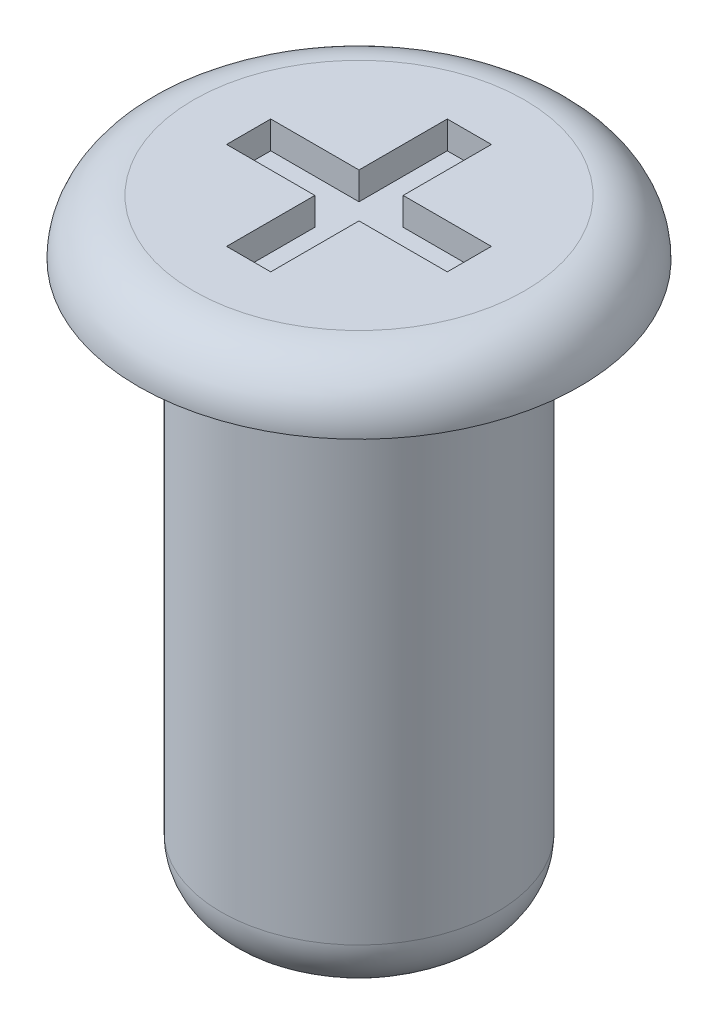
SolidWorks part; units mm, degrees
material "1060 Alloy"
ref_plane "Front Plane" through (0, 0, 0) normal (0, 0, 1) x (1, 0, 0)
ref_plane "Top Plane" through (0, 0, 0) normal (0, 1, 0) x (1, 0, 0)
ref_plane "Right Plane" through (0, 0, 0) normal (1, 0, 0) x (0, 0, -1)
sketch "Sketch1" plane through (0, 0, 0) normal (0, 1, 0) x (1, 0, 0)
  circle A0 centre (0, 0) radius 6.35
  dimension "D1" = 12.7
extrude "Boss-Extrude1" add sketch "Sketch1" along normal blind 25.4
cosmetic thread "Cosmetic Thread3" parameters "D1"=5, "D2"=10.3734
sketch "Sketch2" plane through (0, 25.4, 0) normal (0, 1, 0) x (1, 0, 0)
  circle A0 centre (0, 0) radius 10.16
  dimension "D1" = 20.32
extrude "Boss-Extrude2" add sketch "Sketch2" along normal blind 2.54
fillet "Fillet1" radius 2.54 1 edges at (0, 27.94, 10.16)
sketch "Sketch3" plane through (0, 27.94, 0) normal (0, 1, 0) x (1, 0, 0)
  line L1 (-1.016, -5.08) -> (1.016, -5.08)
  line L2 (-1.016, -5.08) -> (-1.016, 5.08)
  line L3 (-1.016, 5.08) -> (1.016, 5.08)
  line L4 (1.016, -5.08) -> (1.016, 5.08)
  line L5 (-1.016, -5.08) -> (1.016, 5.08) construction
  line L6 (-1.016, 5.08) -> (1.016, -5.08) construction
  line L7 (-5.08, 1.016) -> (5.08, 1.016)
  line L8 (-5.08, 1.016) -> (-5.08, -1.016)
  line L9 (-5.08, -1.016) -> (5.08, -1.016)
  line L10 (5.08, 1.016) -> (5.08, -1.016)
  line L11 (-5.08, 1.016) -> (5.08, -1.016) construction
  line L12 (-5.08, -1.016) -> (5.08, 1.016) construction
  point P0 (0, 0)
  point P6 (0, 0)
  dimension "D1" = 2.032
  dimension "D2" = 2.032
  dimension "D3" = 10.16
  dimension "D4" = 10.16
extrude "Cut-Extrude1" cut sketch "Sketch3" against normal blind 1.27 contours L8 L9 L2 L7 | L2 L7 L4 L3 | L10 L7 L4 L9 | L2 L9 L4 L7 | L9 L2 L1 L4 region at (0, 27.94, 3.048) region at (-3.048, 27.94, 0) region at (0, 27.94, 0) region at (3.048, 27.94, 0) region at (0, 27.94, -3.048)
fillet "Fillet2" radius 2.54 1 edges at (0, 0, 6.35)
